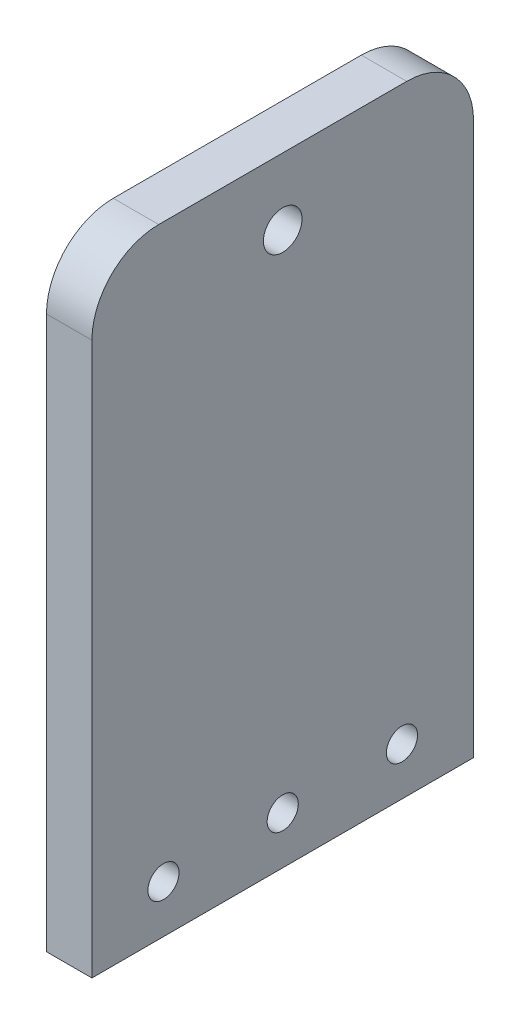
SolidWorks part; units mm, degrees
ref_plane "Front Plane" through (0, 0, 0) normal (0, 0, 1) x (1, 0, 0)
ref_plane "Top Plane" through (0, 0, 0) normal (0, 1, 0) x (1, 0, 0)
ref_plane "Right Plane" through (0, 0, 0) normal (1, 0, 0) x (0, 0, -1)
sketch "Sketch1" plane through (0, 0, 0) normal (1, 0, 0) x (0, 0, -1)
  line L1 (0, 0) -> (40, 0)
  line L2 (0, 0) -> (0, 57.9)
  line L3 (7, 64.9) -> (33, 64.9)
  line L4 (40, 0) -> (40, 57.9)
  arc A1 (33, 64.9) -> (40, 57.9) centre (33, 57.9) cw
  arc A2 (0, 57.9) -> (7, 64.9) centre (7, 57.9) cw
  point P7 (40, 64.9)
  point P10 (0, 64.9)
  dimension "D3" = 7
  dimension "D1" = 40
  dimension "D2" = 57.9
extrude "Boss-Extrude1" add sketch "Sketch1" along normal blind 4.7625 contours L2 L1 L4 region at (0, 32.1977, -20)
ref_axis "Axis1" through (4.7625, 64.9, -20) along (0, -1, 0)
ref_plane "Plane1" through (0, 0, -20) normal (0, 0, -1) x (-1, 0, 0)
hole_wizard "#4 Clearance Hole1" positions "Sketch6" profile "Sketch7" hole size "#4" standard "ANSI Inch" end condition through all
sketch "Sketch6" plane through (4.7625, 0, 0) normal (1, 0, 0) x (0, 0, -1)
  line L0 (0, 0) -> (40, 0) construction
  line L1 (20, -49.3392) -> (20, 49.3392) construction
  point P0 (7.5, 5)
  point P2 (20, 5)
  point P8 (20, 0)
  point P11 (32.5, 5)
  dimension "D1" = 12.5
  dimension "D2" = 5
sketch "Sketch7" plane through (4.7625, 5, -7.5) normal (0, 1, 0) x (0, 0, -1)
  line L0 (0, 0) -> (0, 4.7625)
  line L1 (0, 4.7625) -> (1.6319, 4.7625)
  line L2 (1.6319, 4.7625) -> (1.6319, 0)
  line L5 (1.6319, 0) -> (0, 0)
  line L11 (0, -6.35) -> (0, 107.95) construction
  dimension "Thru Hole Dia." = 3.2639
  dimension "Thru Hole Depth" = 4.7625
sketch "Sketch10" plane through (4.7625, 0, 0) normal (1, 0, 0) x (0, 0, -1)
  line L0 (0, 0) -> (40, 0) construction
  line L1 (20, 64.9) -> (20, -2.7097) construction
  circle A0 centre (20, 57.9) radius 2.025
  dimension "D2" = 4.05
  dimension "D1" = 57.9
extrude "Cut-Extrude1" cut sketch "Sketch10" against normal blind 10
equation "\"Shaft Height\"= 32.5 + 25.4"
equation "\"D2@Sketch1\"=\"Shaft Height\""
equation "\"D1@Sketch10\"=\"Shaft Height\""
equation "\"D1@Boss-Extrude1\"=(3/16)*25.4"
